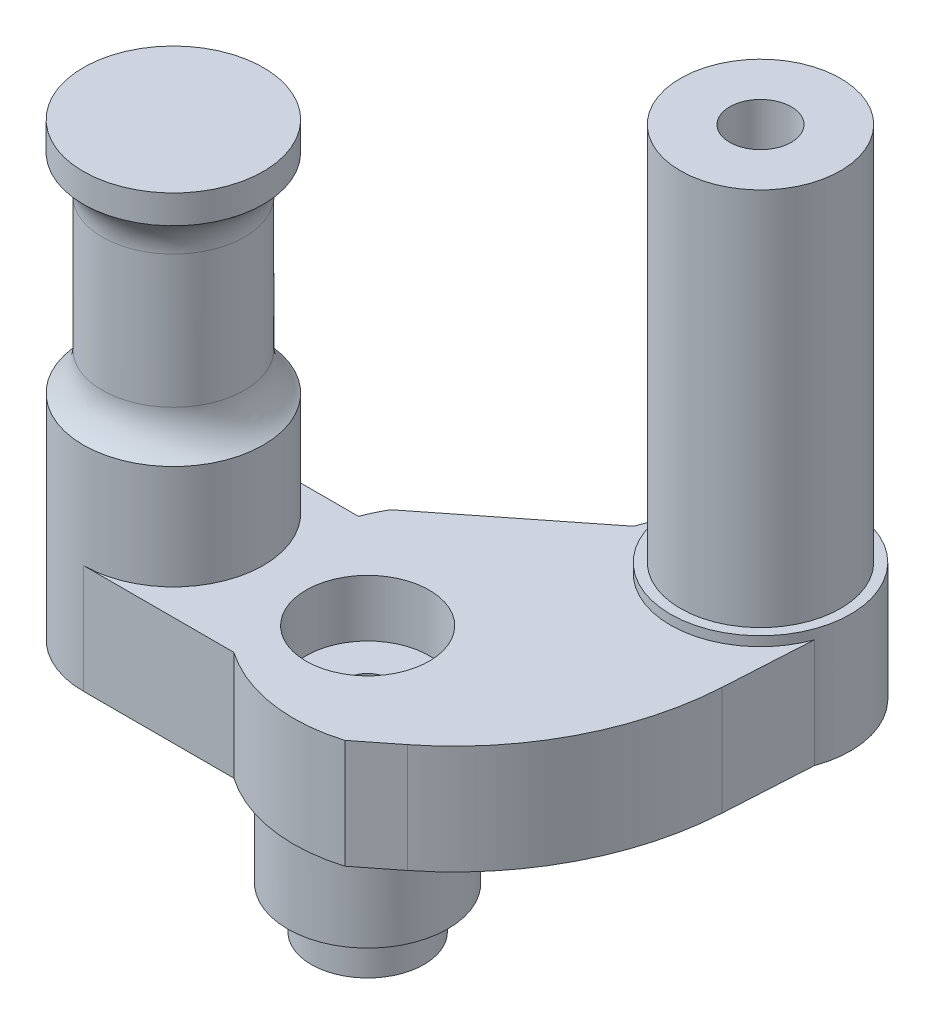
SolidWorks part; units mm, degrees
ref_plane "Спереди" through (0, 0, 0) normal (0, 0, 1) x (1, 0, 0)
ref_plane "Сверху" through (0, 0, 0) normal (0, 1, 0) x (1, 0, 0)
ref_plane "Справа" through (0, 0, 0) normal (1, 0, 0) x (0, 0, -1)
sketch "Эскиз1" plane through (0, 0, 0) normal (0, 1, 0) x (1, 0, 0)
  circle A0 centre (0, 0) radius 5.95
  dimension "D1" = 11.9
extrude "Бобышка-Вытянуть1" add sketch "Эскиз1" along normal blind 4.5
sketch "Эскиз4" plane through (0, 4.5, 0) normal (0, 1, 0) x (1, 0, 0)
  circle A0 centre (0, 0) radius 8.45
  dimension "D1" = 16.9
extrude "Бобышка-Вытянуть4" add sketch "Эскиз4" along normal blind 17.75
sketch "Эскиз6" plane through (0, 22.25, 0) normal (0, 1, 0) x (1, 0, 0)
  line L5 (0, 0) -> (0, 9.5) construction
  line L28 (0, 0) -> (0, -9.5) construction
  line L30 (-7.0021, 9.5) -> (-30, 9.5)
  line L40 (-30, 9.5) -> (-30, -9.5)
  line L41 (-30, -9.5) -> (0, -9.5)
  line L46 (2.3949, 16.0798) -> (10.2606, 37.6908)
  line L47 (10.2606, 37.6908) -> (28.1148, 31.1924)
  line L52 (28.1148, 31.1924) -> (19.0669, 6.3335)
  line L53 (0, -9.5) -> (0.8337, -9.5)
  arc A1 (2.3949, 16.0798) -> (-7.0021, 9.5) centre (-7.0021, 19.5) cw
  arc A4 (5.6703, -8.2525) -> (19.0669, 6.3335) centre (-9.4167, 19.0492) ccw
  arc A5 (5.6703, -8.2525) -> (0.8337, -9.5) centre (0.8337, 0.5) cw
  dimension "D3" = 110
  dimension "D4" = 19
  dimension "D6" = 30
  dimension "D2" = 30
  dimension "D5" = 10
  dimension "D7" = 10
  dimension "D1" = 19
extrude "Бобышка-Вытянуть6" add sketch "Эскиз6" along normal blind 5.75 and the other way blind 5.75
sketch "Эскиз12" plane through (0, 28, 0) normal (0, 1, 0) x (1, 0, 0)
  line L0 (19.1877, 34.4416) -> (15.9385, 25.5145) construction
  line L2 (28.1148, 31.1924) -> (10.2606, 37.6908) construction
  line L3 (10.2606, 37.6908) -> (2.3949, 16.0798) construction
  circle A0 centre (15.9385, 25.5145) radius 9.5
  dimension "D1" = 19
  dimension "D2" = 9.5
extrude "Бобышка-Вытянуть10" add sketch "Эскиз12" along normal blind 1
sketch "Эскиз7" plane through (0, 0, 0) normal (0, -1, 0) x (1, 0, 0)
  circle A0 centre (0, 0) radius 2.3
  dimension "D1" = 4.6
extrude "Вырез-Вытянуть1" cut sketch "Эскиз7" against normal through all
sketch "Эскиз8" plane through (0, 28, 0) normal (0, 1, 0) x (1, 0, 0)
  circle A0 centre (0, 0) radius 6.5
  dimension "D1" = 13
extrude "Вырез-Вытянуть2" cut sketch "Эскиз8" against normal blind 6
sketch "Эскиз9" plane through (0, 28, 0) normal (0, -1, 0) x (1, 0, 0)
  line L0 (-30, 0) -> (-20.5, 0) construction
  line L1 (-30, -9.5) -> (-30, 9.5) construction
  circle A1 centre (-20.5, 0) radius 9.5
  dimension "D1" = 19
  dimension "D2" = 9.5
extrude "Бобышка-Вытянуть7" add sketch "Эскиз9" against normal blind 36 from surface starting at face at (0, 28, 6.5)
sketch "Эскиз10" plane through (0, 29, 0) normal (0, 1, 0) x (1, 0, 0)
  circle A1 centre (15.9385, 25.5145) radius 8.45
  dimension "D1" = 16.9
extrude "Бобышка-Вытянуть8" add sketch "Эскиз10" along normal blind 40
sketch "Эскиз13" plane through (0, 16.5, 0) normal (0, -1, 0) x (1, 0, 0)
  circle A0 centre (0, 0) radius 9.5
  circle A1 centre (0, 0) radius 2.3
extrude "Бобышка-Вытянуть11" add sketch "Эскиз13" along normal blind 1
sketch "Эскиз14" plane through (0, 69, 0) normal (0, 1, 0) x (1, 0, 0)
  circle A0 centre (15.9385, 25.5145) radius 3.25
  dimension "D1" = 6.5
extrude "Вырез-Вытянуть3" cut sketch "Эскиз14" against normal blind 8
sketch "Эскиз15" plane through (0, 28, 0) normal (0, 1, 0) x (1, 0, 0)
  line L10 (-20.5, 9.5) -> (-20.5, 16.9474)
  line L11 (-20.5, 16.9474) -> (-42.1293, 16.9474)
  line L12 (-42.1293, 16.9474) -> (-42.1293, -12.7423)
  line L13 (-42.1293, -12.7423) -> (-20.5, -12.7423)
  line L14 (-20.5, -12.7423) -> (-20.5, -9.5)
  line L25 (7.1554, 29.1349) -> (-1.2552, 32.6016)
  line L26 (-1.2552, 32.6016) -> (4.6311, 46.882)
  line L27 (4.6311, 46.882) -> (38.7847, 32.804)
  line L28 (38.7847, 32.804) -> (32.8985, 18.5237)
  line L29 (32.8985, 18.5237) -> (24.7216, 21.8942)
  arc A3 (-20.5, 9.5) -> (-20.5, -9.5) centre (-20.5, 0) ccw
  arc A5 (24.7216, 21.8942) -> (7.1554, 29.1349) centre (15.9385, 25.5145) ccw
  dimension "D1" = 9.5
extrude "Вырез-Вытянуть4" cut sketch "Эскиз15" against normal blind 18
sketch "Эскиз16" plane through (0, 28, 0) normal (0, 1, 0) x (1, 0, 0)
  circle A0 centre (-20.5, 0) radius 7.5
  circle A1 centre (-20.5, 0) radius 14.9564
  dimension "D1" = 15
extrude "Вырез-Вытянуть5" cut sketch "Эскиз16" along normal blind 22 from offset 11
fillet "Скругление2" radius 5 2 edges at (-20.5, 39, 7.5) (-20.5, 61, 7.5)
sketch "Эскиз18" plane through (0, 16.5, 0) normal (0, -1, 0) x (1, 0, 0)
  line L0 (0, 0) -> (14.2522, -11.3123) construction
  line L1 (9.2785, 11.6909) -> (12.9726, 8.7754)
  line L2 (-9.3719, -11.8075) -> (5.4135, -23.4765)
  line L3 (24.3377, -13.057) -> (24.8656, -22.2653)
  line L4 (5.4135, -23.4765) -> (24.8656, -22.2653)
  line L5 (0, 0) -> (-9.3719, -11.8075) construction
  line L6 (14.2522, -11.3123) -> (24.8656, -22.2653) construction
  circle A0 centre (0, 0) radius 7.5
  arc A1 (9.2785, 11.6909) -> (-9.3719, -11.8075) centre (4.5907, -3.7389) ccw
  arc A2 (12.9726, 8.7754) -> (24.3377, -13.057) centre (-5.6131, -14.774) cw
  dimension "D2" = 30
  dimension "D1" = 30
  dimension "D3" = 5.9206
  dimension "D4" = 90.282
  dimension "D5" = 19.452
  dimension "D6" = 9.2083
  dimension "D7" = 18.8354
  dimension "D8" = 2.9155
  dimension "D9" = 15.0748
  dimension "D10" = 18.196
  dimension "D11" = 15.2516
  dimension "D12" = 172.538
extrude "Бобышка-Вытянуть12" add sketch "Эскиз18" against normal up to surface (11.5 mm away) up to face at (4.4867, 28, -7.5158)
